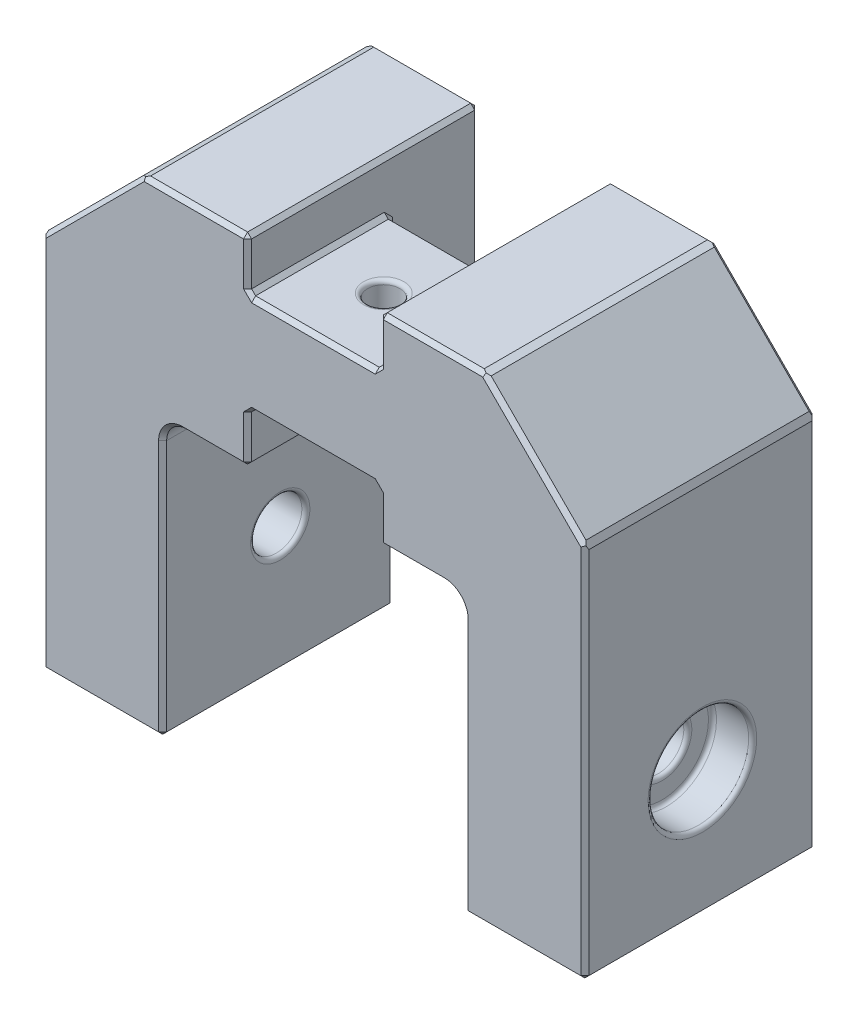
SolidWorks part; units mm, degrees
note: The reader was unsure of these and kept them because the rebuilt part matched: shared geometry of "Sketch1<4>", "Sketch2<4>".
ref_plane "Front Plane" through (0, 0, 0) normal (0, 0, 1) x (1, 0, 0)
ref_plane "Top Plane" through (0, 0, 0) normal (0, 1, 0) x (1, 0, 0)
ref_plane "Right Plane" through (0, 0, 0) normal (1, 0, 0) x (0, 0, -1)
sketch "Sketch1" plane through (0, 0, 0) normal (0, 0, 1) x (1, 0, 0)
  line L0 (0, 45.3438) -> (0, 0) construction
  line L1 (0, 0) -> (45.3438, 0) construction
  line L2 (-15, 4.1) -> (15, 4.1) construction
  line L3 (-12.5, 15) -> (12.5, 15) construction
  line L4 (-15, 12.5) -> (-15, -12.5) construction
  line L5 (-12.5, -15) -> (12.5, -15) construction
  line L6 (15, 12.5) -> (15, -12.5) construction
  line L7 (-15, -4.1) -> (15, -4.1) construction
  line L8 (-15, -12.5) -> (-15, 13)
  line L9 (-13, 15) -> (13, 15)
  line L10 (15, 13) -> (15, -12.5)
  line L11 (15, -12.5) -> (27, -12.5)
  line L12 (27, -12.5) -> (27, 35)
  line L13 (27, 35) -> (-27, 35)
  line L14 (-27, 35) -> (-27, -12.5)
  line L15 (-27, -12.5) -> (-15, -12.5)
  line L16 (6.55, 29.9) -> (6.55, 20.1)
  line L17 (-6.55, 20.1) -> (6.55, 20.1)
  line L18 (-6.55, 20.1) -> (-6.55, 15)
  line L19 (-6.55, 15) -> (6.55, 15)
  line L20 (6.55, 20.1) -> (6.55, 15)
  line L21 (-6.55, 35) -> (6.55, 35)
  line L22 (-6.55, 35) -> (-6.55, 29.9)
  line L23 (-6.55, 29.9) -> (6.55, 29.9)
  line L24 (6.55, 35) -> (6.55, 29.9)
  line L25 (-6.55, 29.9) -> (-6.55, 20.1)
  arc A0 (-15, -12.5) -> (-12.5, -15) centre (-12.5, -12.5) ccw construction
  arc A1 (12.5, -15) -> (15, -12.5) centre (12.5, -12.5) ccw construction
  arc A2 (15, 12.5) -> (12.5, 15) centre (12.5, 12.5) ccw construction
  arc A3 (-12.5, 15) -> (-15, 12.5) centre (-12.5, 12.5) ccw construction
  arc A4 (15, 13) -> (13, 15) centre (13, 13) ccw
  arc A5 (-13, 15) -> (-15, 13) centre (-13, 13) ccw
  point P10 (-15, -15)
  point P13 (15, -15)
  point P18 (-15, 15)
  point P33 (-15, 15)
  dimension "D3" = 2.5
  dimension "D5" = 2
  dimension "D1" = 30
  dimension "D2" = 30
  dimension "D4" = 8.2
  dimension "D6" = 12
  dimension "D7" = 20
  dimension "D8" = 5.1
  dimension "D9" = 5.1
  dimension "D10" = 13.1
extrude "Boss-Extrude1" add sketch "Sketch1" along normal blind 23 contours A4 L10 L11 L12 L13 L24 L16 L20 L9 | A5 L9 L18 L25 L22 L13 L14 L15 L8 | L23 L25 L17 L16
extrude "Cut-Extrude1" cut sketch "Sketch1<4>" along normal blind 9 contours L23 L25 L17 L16
sketch "Sketch1<4>" plane through (0, 0, 0) normal (0, 0, 1) x (1, 0, 0) same geometry as "Sketch1"
chamfer "Chamfer4" distance 10 angle 45 2 edges at (27, 35, 11.5) (-27, 35, 11.5)
chamfer "Chamfer5" distance 0.4 angle 45 52 edges at (-6.55, 29.9, 16) (-6.55, 20.1, 16) (6.55, 20.1, 16) (6.55, 29.9, 16) (-6.55, 25, 9) (0, 20.1, 9) (6.55, 25, 9) (0, 29.9, 9) (-27, -12.5, 11.5) (-15, -12.5, 11.5) (15, -12.5, 11.5) (27, -12.5, 11.5) (21, -12.5, 0) (21, -12.5, 23) (15, 0.25, 0) (15, 0.25, 23) (14.4142, 14.4142, 0) (14.4142, 14.4142, 23) (9.775, 15, 0) (9.775, 15, 23) (6.55, 17.55, 23) (0, 20.1, 23) (-6.55, 17.55, 23) (-9.775, 15, 0) (-9.775, 15, 23) (-14.4142, 14.4142, 0) (-14.4142, 14.4142, 23) (-15, 0.25, 0) (-15, 0.25, 23) (-21, -12.5, 0) (-21, -12.5, 23) (-27, 6.25, 23) (-27, 6.25, 0) (-22, 30, 23) (-22, 30, 0) (-11.775, 35, 0) (-11.775, 35, 23) (27, 6.25, 0) (27, 6.25, 23) (22, 30, 23) (22, 30, 0) (11.775, 35, 23) (11.775, 35, 0) (6.55, 25, 0) (6.55, 15, 11.5) (6.55, 35, 11.5) (6.55, 32.45, 23) (0, 29.9, 23) (-6.55, 32.45, 23) (-6.55, 15, 11.5) (-6.55, 25, 0) (-6.55, 35, 11.5)
chamfer "Chamfer6" distance 0.4 4 edges at (-27, 25, 11.5) (-17, 35, 11.5) (17, 35, 11.5) (27, 25, 11.5)
sketch "Sketch2" plane through (27, 0, 0) normal (1, 0, 0) x (0, 0, -1)
  line L0 (0, 0) -> (-22.6, 0) construction
  line L1 (-22.6, 24.6) -> (-22.6, -12.1) construction
  line L2 (-0.4, 4.1) -> (-22.6, 4.1) construction
  line L3 (-0.4, -12.1) -> (-0.4, 24.6) construction
  line L4 (0, -4.1) -> (-22.6, -4.1) construction
  line L5 (0, -12.5) -> (0, 35) construction
  circle A0 centre (-11.3, 0) radius 5
  circle A1 centre (-11.3, 0) radius 2.55
  dimension "D1" = 5.1
  dimension "D2" = 10
extrude "Cut-Extrude2" cut sketch "Sketch2" against normal through all contours A1
extrude "Cut-Extrude3" cut sketch "Sketch2<4>" against normal blind 4
sketch "Sketch2<4>" plane through (27, 0, 0) normal (1, 0, 0) x (0, 0, -1) same geometry as "Sketch2"
sketch "Sketch5" plane through (-27, 0, 0) normal (-1, 0, 0) x (0, 0, 1)
  circle A0 centre (11.3, 0) radius 5
  circle M2 centre (11.3, 0) radius 2.55
  dimension "D1" = 10
extrude "Cut-Extrude4" cut sketch "Sketch5" against normal blind 4 contours A0 M2
fillet "Fillet1" radius 0.4 2 edges at (-27, -5, 11.3) (27, 5, 11.3)
sketch "Sketch6" plane through (0, 29.9, 0) normal (0, 1, 0) x (1, 0, 0)
  line L0 (0, 0) -> (0, -22.6) construction
  line L1 (-6.15, -22.6) -> (6.15, -22.6) construction
  circle A0 centre (0, -16) radius 1.6
  dimension "D1" = 16
extrude "Cut-Extrude5" cut sketch "Sketch6" against normal through all
fillet "Fillet2" radius 0.4 8 edges at (-23, -5, 11.3) (-23, -2.55, 11.3) (23, 5, 11.3) (23, 2.55, 11.3) (-15, -2.55, 11.3) (15, 2.55, 11.3) (0, 20.1, 17.6) (0, 29.9, 17.6)
